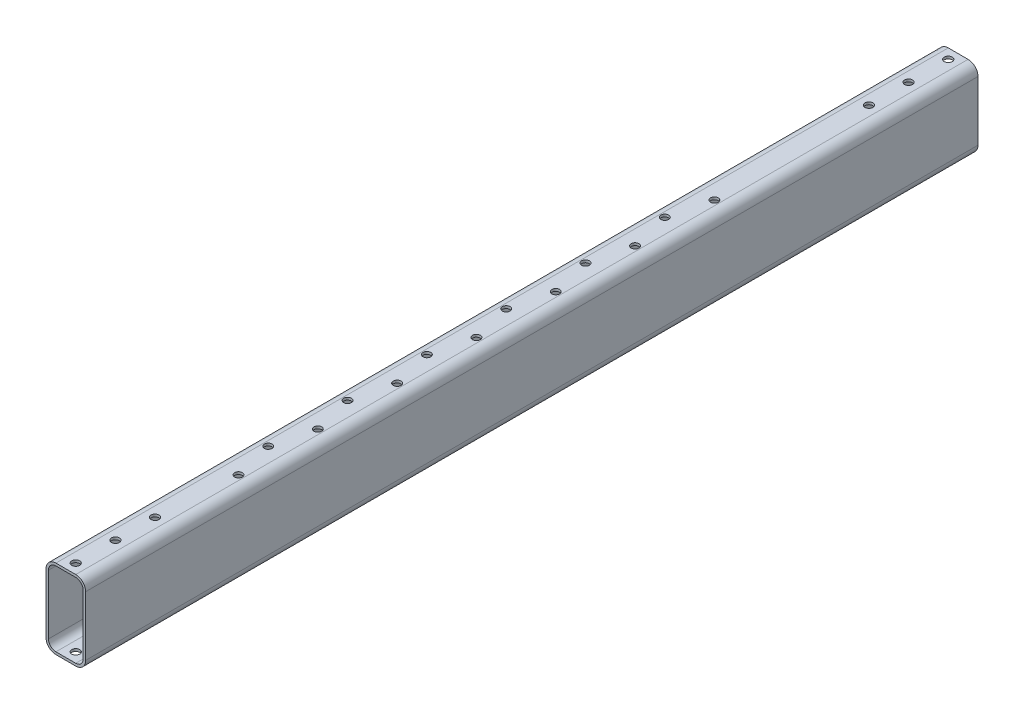
SolidWorks part; units mm, degrees
material "6061-T6 (SS)"
ref_plane "Front Plane" through (0, 0, 0) normal (0, 0, 1) x (1, 0, 0)
ref_plane "Top Plane" through (0, 0, 0) normal (0, 1, 0) x (1, 0, 0)
ref_plane "Right Plane" through (0, 0, 0) normal (1, 0, 0) x (0, 0, -1)
sketch "Sketch1" plane through (0, 0, 0) normal (0, 0, 1) x (1, 0, 0)
  line L1 (-6.35, -25.4) -> (6.35, -25.4)
  line L2 (-12.7, -19.05) -> (-12.7, 19.05)
  line L3 (-6.35, 25.4) -> (6.35, 25.4)
  line L4 (12.7, -19.05) -> (12.7, 19.05)
  line L5 (-12.7, -25.4) -> (12.7, 25.4) construction
  line L6 (-12.7, 25.4) -> (12.7, -25.4) construction
  arc A0 (-12.7, -19.05) -> (-6.35, -25.4) centre (-6.35, -19.05) ccw
  arc A1 (6.35, -25.4) -> (12.7, -19.05) centre (6.35, -19.05) ccw
  arc A2 (6.35, 25.4) -> (12.7, 19.05) centre (6.35, 19.05) cw
  arc A3 (-12.7, 19.05) -> (-6.35, 25.4) centre (-6.35, 19.05) cw
  point P0 (0, 0)
  dimension "D3" = 6.35
  dimension "D1" = 50.8
  dimension "D2" = 25.4
extrude "Extrude-Thin1" add sketch "Sketch1" along normal blind 571.5 thin thin type one direction reverse wall 1.5875
hole_wizard "#10 Clearance Hole1" positions "3DSketch1" profile "Sketch3" hole size "#10" standard "ANSI Inch" end condition through all
sketch3d "3DSketch1"
  line L1 (6.35, 25.4, 0) -> (-6.35, 25.4, 0) construction
  line L6 (0, 25.4, 571.5) -> (0, 25.4, 0) construction
  line L7 (6.35, 25.4, 571.5) -> (-6.35, 25.4, 571.5) construction
  point P57 (0, 25.4, 6.35)
  point P59 (0, 25.4, 31.75)
  point P61 (0, 25.4, 57.15)
  point P63 (0, 25.4, 539.75)
  point P65 (0, 25.4, 514.35)
  point P67 (0, 25.4, 565.15)
  dimension "D1" = 25.4
  dimension "D2" = 25.4
  dimension "D3" = 6.35
  dimension "D4" = 25.4
  dimension "D5" = 25.4
  dimension "D6" = 6.35
sketch "Sketch3" plane through (0, 25.4, 565.15) normal (1, 0, 0) x (0, 0, 1)
  line L0 (0, 0) -> (0, 50.8)
  line L1 (0, 50.8) -> (2.5527, 50.8)
  line L2 (2.5527, 50.8) -> (2.5527, 0)
  line L5 (2.5527, 0) -> (0, 0)
  line L11 (0, -6.35) -> (0, 107.95) construction
  dimension "Thru Hole Dia." = 5.1054
  dimension "Thru Hole Depth" = 50.8
hole_wizard "3/16 (0.195) Diameter Hole1" positions "Sketch4" profile "Sketch5" hole size "3/16" standard "ANSI Inch" end condition up to next
sketch "Sketch4" plane through (0, 25.4, 0) normal (0, 1, 0) x (1, 0, 0)
  point P0 (3.175, -464.0947)
  point P3 (-3.175, -438.6947)
  point P6 (3.175, -413.2947)
  point P9 (-3.175, -387.8947)
  point P12 (3.175, -362.4947)
  point P15 (-3.175, -337.0947)
  point P18 (3.175, -311.6947)
  point P21 (-3.175, -286.2947)
  point P24 (3.175, -260.8947)
  point P29 (3.175, -210.0947)
  point P32 (-3.175, -184.6947)
  point P35 (3.175, -159.2947)
  point P41 (-3.175, -235.4947)
sketch "Sketch5" plane through (3.175, 25.4, 464.0947) normal (1, 0, 0) x (0, 0, 1)
  line L0 (0, 0) -> (0, 1.5875)
  line L1 (0, 1.5875) -> (2.4765, 1.5875)
  line L2 (2.4765, 1.5875) -> (2.4765, 0)
  line L5 (2.4765, 0) -> (0, 0)
  line L11 (0, -6.35) -> (0, 107.95) construction
  dimension "Thru Hole Dia." = 4.953
  dimension "Thru Hole Depth" = 1.5875
